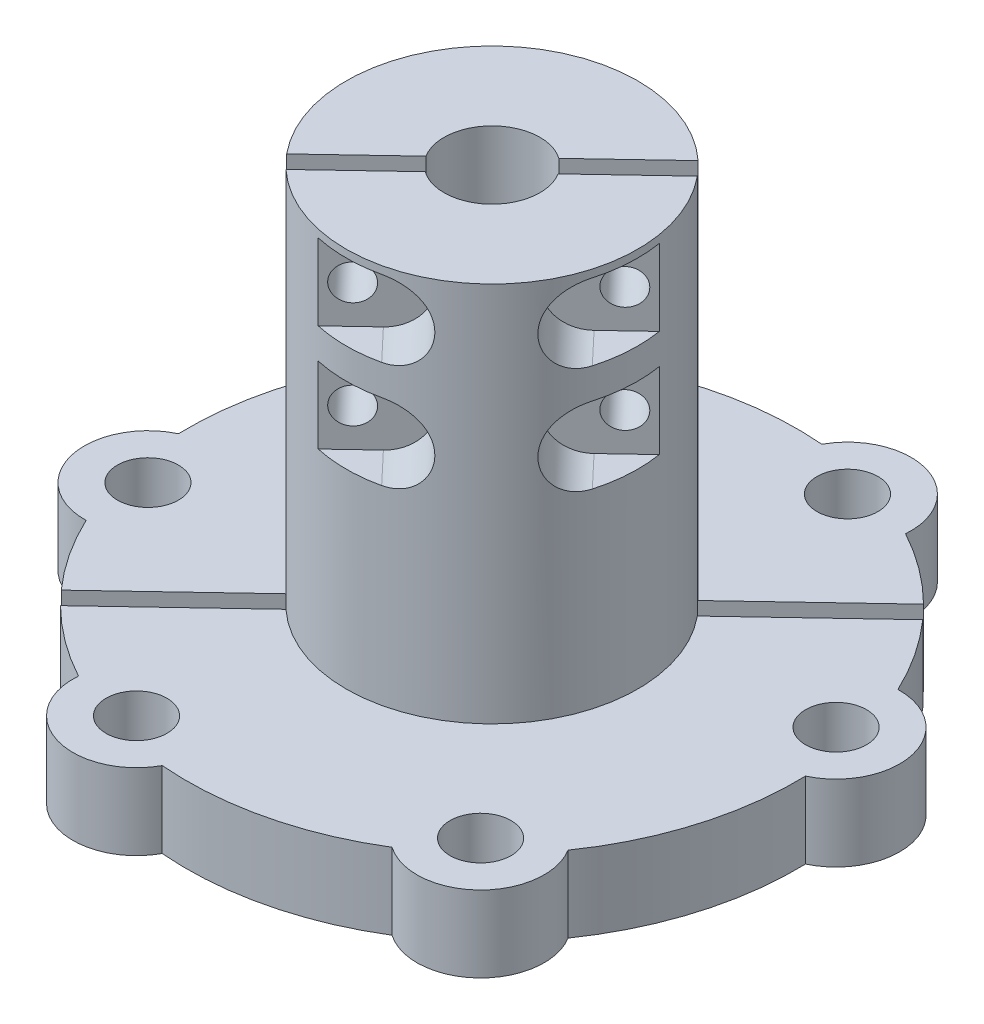
SolidWorks part; units mm, degrees
ref_plane "Front" through (0, 0, 0) normal (0, 0, 1) x (1, 0, 0)
ref_plane "Top" through (0, 0, 0) normal (0, 1, 0) x (1, 0, 0)
ref_plane "Right" through (0, 0, 0) normal (1, 0, 0) x (0, 0, -1)
sketch "Sketch1" plane through (0, 0, 0) normal (0, 1, 0) x (1, 0, 0)
  circle A0 centre (0, 0) radius 29.3688
  circle A1 centre (0, 0) radius 4
  dimension "D1" = 58.7375
  dimension "D2" = 8
extrude "Boss-Extrude1" add sketch "Sketch1" along normal blind 6.35
sketch "Sketch3" plane through (0, 6.35, 0) normal (0, 1, 0) x (1, 0, 0)
  circle A0 centre (0, 0) radius 4 construction
  circle A1 centre (0, 0) radius 4
  circle A2 centre (0, 0) radius 12.1539
  dimension "D1" = 24.3078
extrude "Boss-Extrude2" add sketch "Sketch3" along normal blind 31.75
sketch "Sketch4" plane through (0, 6.35, 0) normal (0, 1, 0) x (1, 0, 0)
  circle A0 centre (0, 0) radius 51.9218
  arc A1 (25.4208, 0.7099) -> (23.0191, 10.8093) centre (23.1665, 5.5091) ccw
  arc A2 (23.0191, 10.8093) -> (12.0949, 22.3703) centre (0, 0) ccw
  arc A3 (12.0949, 22.3703) -> (2.1481, 25.3398) centre (6.8115, 22.8166) ccw
  arc A4 (2.1481, 25.3398) -> (-13.3267, 21.6591) centre (0, 0) ccw
  arc A5 (-13.3267, 21.6591) -> (-20.8715, 14.5293) centre (-16.3548, 17.3065) ccw
  arc A6 (-20.8715, 14.5293) -> (-25.4207, -0.7121) centre (0, 0) ccw
  arc A7 (-25.4207, -0.7121) -> (-23.0182, -10.8112) centre (-23.166, -5.5111) ccw
  arc A8 (-23.0182, -10.8112) -> (-12.0943, -22.3707) centre (0, 0) ccw
  arc A9 (-12.0943, -22.3707) -> (-2.1466, -25.3399) centre (-6.811, -22.8186) ccw
  arc A10 (-2.1466, -25.3399) -> (13.3255, -21.6599) centre (0, 0) ccw
  arc A11 (13.3255, -21.6599) -> (20.8711, -14.5299) centre (16.3552, -17.3085) ccw
  arc A12 (25.6787, 0.5533) -> (23.1789, 11.0653) centre (23.1665, 5.5091) ccw
  arc A13 (21.1727, -14.5402) -> (25.6787, 0.5533) centre (0, 0) ccw
  arc A14 (13.3188, -21.9616) -> (21.1727, -14.5402) centre (16.3552, -17.3085) ccw
  arc A15 (-2.0047, -25.6063) -> (13.3188, -21.9616) centre (0, 0) ccw
  arc A16 (-12.359, -22.5157) -> (-2.0047, -25.6063) centre (-6.811, -22.8186) ccw
  arc A17 (-23.178, -11.0673) -> (-12.359, -22.5157) centre (0, 0) ccw
  arc A18 (-25.6787, -0.5554) -> (-23.178, -11.0673) centre (-23.166, -5.5111) ccw
  arc A19 (-21.1731, 14.5397) -> (-25.6787, -0.5554) centre (0, 0) ccw
  arc A20 (-13.3201, 21.9608) -> (-21.1731, 14.5397) centre (-16.3548, 17.3065) ccw
  arc A21 (2.0063, 25.6062) -> (-13.3201, 21.9608) centre (0, 0) ccw
  arc A22 (12.3596, 22.5154) -> (2.0063, 25.6062) centre (6.8115, 22.8166) ccw
  arc A23 (23.1789, 11.0653) -> (12.3596, 22.5154) centre (0, 0) ccw
  arc A24 (25.6787, 0.5533) -> (23.1789, 11.0653) centre (23.1665, 5.5091) ccw construction
  arc A25 (21.1727, -14.5402) -> (25.6787, 0.5533) centre (0, 0) ccw construction
  arc A26 (13.3188, -21.9616) -> (21.1727, -14.5402) centre (16.3552, -17.3085) ccw construction
  arc A27 (-2.0047, -25.6063) -> (13.3188, -21.9616) centre (0, 0) ccw construction
  arc A28 (-12.359, -22.5157) -> (-2.0047, -25.6063) centre (-6.811, -22.8186) ccw construction
  arc A29 (-23.178, -11.0673) -> (-12.359, -22.5157) centre (0, 0) ccw construction
  arc A30 (-25.6787, -0.5554) -> (-23.178, -11.0673) centre (-23.166, -5.5111) ccw construction
  arc A31 (-21.1731, 14.5397) -> (-25.6787, -0.5554) centre (0, 0) ccw construction
  arc A32 (-13.3201, 21.9608) -> (-21.1731, 14.5397) centre (-16.3548, 17.3065) ccw construction
  arc A33 (2.0063, 25.6062) -> (-13.3201, 21.9608) centre (0, 0) ccw construction
  arc A34 (12.3596, 22.5154) -> (2.0063, 25.6062) centre (6.8115, 22.8166) ccw construction
  arc A35 (23.1789, 11.0653) -> (12.3596, 22.5154) centre (0, 0) ccw construction
  arc A36 (20.8711, -14.5299) -> (25.4208, 0.7099) centre (0, 0) ccw
  dimension "D2" = 0.254
  dimension "D1" = 0
extrude "Cut-Extrude1" cut sketch "Sketch4" against normal through all
sketch "Sketch5" plane through (0, 6.35, 0) normal (0, 1, 0) x (1, 0, 0)
  circle A0 centre (-23.166, -5.5111) radius 2.54 construction
  circle A1 centre (-6.811, -22.8186) radius 2.54 construction
  circle A2 centre (16.3552, -17.3085) radius 2.54 construction
  circle A3 centre (23.1665, 5.5091) radius 2.54 construction
  circle A4 centre (6.8115, 22.8166) radius 2.54 construction
  circle A5 centre (-16.3548, 17.3065) radius 2.54 construction
  circle A6 centre (-23.166, -5.5111) radius 2.54
  circle A7 centre (-6.811, -22.8186) radius 2.54
  circle A8 centre (16.3552, -17.3085) radius 2.54
  circle A9 centre (23.1665, 5.5091) radius 2.54
  circle A10 centre (6.8115, 22.8166) radius 2.54
  circle A11 centre (-16.3548, 17.3065) radius 2.54
extrude "Cut-Extrude2" cut sketch "Sketch5" against normal through all
sketch "Sketch6" plane through (0, 0, 0) normal (0, -1, 0) x (1, 0, 0)
  circle A0 centre (0, 0) radius 11.1125
  dimension "D1" = 22.225
extrude "Cut-Extrude3" cut sketch "Sketch6" against normal blind 12.7
sketch "Outline" plane through (0, 0, 0) normal (0, -1, 0) x (1, 0, 0)
  circle A0 centre (0, 0) radius 11.1125 construction
  circle A1 centre (0, 0) radius 11.1125
  arc A12 (25.4208, -0.7099) -> (20.8711, 14.5299) centre (0, 0) ccw
  arc A13 (20.8711, 14.5299) -> (13.3255, 21.6599) centre (16.3552, 17.3085) ccw
  arc A14 (13.3255, 21.6599) -> (-2.1466, 25.3399) centre (0, 0) ccw
  arc A15 (-2.1466, 25.3399) -> (-12.0943, 22.3707) centre (-6.811, 22.8186) ccw
  arc A16 (-12.0943, 22.3707) -> (-23.0182, 10.8112) centre (0, 0) ccw
  arc A17 (-23.0182, 10.8112) -> (-25.4207, 0.7121) centre (-23.166, 5.5111) ccw
  arc A18 (-25.4207, 0.7121) -> (-20.8715, -14.5293) centre (0, 0) ccw
  arc A19 (-20.8715, -14.5293) -> (-13.3267, -21.6591) centre (-16.3548, -17.3065) ccw
  arc A20 (-13.3267, -21.6591) -> (2.1481, -25.3398) centre (0, 0) ccw
  arc A21 (2.1481, -25.3398) -> (12.0949, -22.3703) centre (6.8115, -22.8166) ccw
  arc A22 (12.0949, -22.3703) -> (23.0191, -10.8093) centre (0, 0) ccw
  arc A23 (23.0191, -10.8093) -> (25.4208, -0.7099) centre (23.1665, -5.5091) ccw
  arc A24 (25.4208, -0.7099) -> (20.8711, 14.5299) centre (0, 0) ccw
  arc A25 (20.8711, 14.5299) -> (13.3255, 21.6599) centre (16.3552, 17.3085) ccw
  arc A26 (13.3255, 21.6599) -> (-2.1466, 25.3399) centre (0, 0) ccw
  arc A27 (-2.1466, 25.3399) -> (-12.0943, 22.3707) centre (-6.811, 22.8186) ccw
  arc A28 (-12.0943, 22.3707) -> (-23.0182, 10.8112) centre (0, 0) ccw
  arc A29 (-23.0182, 10.8112) -> (-25.4207, 0.7121) centre (-23.166, 5.5111) ccw
  arc A30 (-25.4207, 0.7121) -> (-20.8715, -14.5293) centre (0, 0) ccw
  arc A31 (-20.8715, -14.5293) -> (-13.3267, -21.6591) centre (-16.3548, -17.3065) ccw
  arc A32 (-13.3267, -21.6591) -> (2.1481, -25.3398) centre (0, 0) ccw
  arc A33 (2.1481, -25.3398) -> (12.0949, -22.3703) centre (6.8115, -22.8166) ccw
  arc A34 (12.0949, -22.3703) -> (23.0191, -10.8093) centre (0, 0) ccw
  arc A35 (23.0191, -10.8093) -> (25.4208, -0.7099) centre (23.1665, -5.5091) ccw
  dimension "D1" = 0
sketch "Sketch7" plane through (0, 0, 0) normal (0, -1, 0) x (1, 0, 0)
  line L0 (-18.4831, 17.4669) -> (18.4841, -17.4659) construction
  line L1 (-23.8841, 21.4785) -> (22.7947, -22.6313)
  line L2 (-22.7937, 22.6323) -> (23.885, -21.4775)
  line L3 (-17.938, 18.0438) -> (19.0293, -16.889) construction
  line L4 (-19.0283, 16.89) -> (17.9389, -18.0428) construction
  arc A0 (-12.0943, 22.3707) -> (-23.0182, 10.8112) centre (0, 0) ccw construction
  arc A1 (12.0949, -22.3703) -> (23.0191, -10.8093) centre (0, 0) ccw construction
  arc A2 (-22.7937, 22.6323) -> (-23.8841, 21.4785) centre (0, 0) ccw
  arc A3 (22.7947, -22.6313) -> (23.885, -21.4775) centre (0, 0) ccw
  dimension "D1" = 0.7937
  dimension "D2" = 0.7937
extrude "Slot" cut sketch "Sketch7" against normal through all
ref_plane "Plane1" through (-25.6223, 0, -27.1146) normal (-0.6868, 0, -0.7268) x (-0.7268, 0, 0.6868)
sketch "Sketch8" plane through (-25.6223, 0, -27.1146) normal (-0.6868, 0, -0.7268) x (-0.7268, 0, 0.6868)
  line L0 (8.0241, 38.1) -> (8.0241, 34.29) construction
  line L1 (8.0241, 34.29) -> (8.0241, 25.4) construction
  line L2 (3.9203, 12.7) -> (-3.9203, 12.7) construction
  line L3 (0, 12.7) -> (0, 58.6753) construction
  line L8 (12.1279, 38.1) -> (3.9203, 38.1)
  line L9 (3.9203, 38.1) -> (3.9203, 12.7)
  line L10 (3.9203, 12.7) -> (11.0841, 12.7)
  line L11 (11.0841, 12.7) -> (11.0841, 0)
  line L12 (11.0841, 0) -> (25.4183, 0)
  line L13 (25.4183, 0) -> (25.4183, 6.35)
  line L14 (25.4183, 6.35) -> (12.1279, 6.35)
  line L15 (12.1279, 6.35) -> (12.1279, 38.1)
  line L16 (12.1279, 38.1) -> (3.9203, 38.1) construction
  line L17 (3.9203, 38.1) -> (3.9203, 12.7) construction
  line L18 (3.9203, 12.7) -> (11.0841, 12.7) construction
  line L19 (11.0841, 12.7) -> (11.0841, 0) construction
  line L20 (11.0841, 0) -> (25.4183, 0) construction
  line L21 (25.4183, 0) -> (25.4183, 6.35) construction
  line L22 (25.4183, 6.35) -> (12.1279, 6.35) construction
  line L23 (12.1279, 6.35) -> (12.1279, 38.1) construction
  line L24 (-12.1279, 6.35) -> (-25.4183, 6.35)
  line L25 (-25.4183, 6.35) -> (-25.4183, 0)
  line L26 (-25.4183, 0) -> (-11.0841, 0)
  line L27 (-11.0841, 0) -> (-11.0841, 12.7)
  line L28 (-11.0841, 12.7) -> (-3.9203, 12.7)
  line L29 (-3.9203, 12.7) -> (-3.9203, 38.1)
  line L30 (-3.9203, 38.1) -> (-12.1279, 38.1)
  line L31 (-12.1279, 38.1) -> (-12.1279, 6.35)
  line L32 (-12.1279, 6.35) -> (-25.4183, 6.35) construction
  line L33 (-25.4183, 6.35) -> (-25.4183, 0) construction
  line L34 (-25.4183, 0) -> (-11.0841, 0) construction
  line L35 (-11.0841, 0) -> (-11.0841, 12.7) construction
  line L36 (-11.0841, 12.7) -> (-3.9203, 12.7) construction
  line L37 (-3.9203, 12.7) -> (-3.9203, 38.1) construction
  line L38 (-3.9203, 38.1) -> (-12.1279, 38.1) construction
  line L39 (-12.1279, 38.1) -> (-12.1279, 6.35) construction
  circle A0 centre (8.0241, 34.29) radius 1.4732
  circle A1 centre (8.0241, 25.4) radius 1.4732
  circle A2 centre (-8.0241, 34.29) radius 1.4732
  circle A3 centre (-8.0241, 25.4) radius 1.4732
  dimension "D4" = 2.9464
  dimension "D3" = 3.81
  dimension "D5" = 8.89
  dimension "D1" = 0
  dimension "D2" = 0
extrude "No4-40 Holes" cut sketch "Sketch8" against normal through all
sketch "Sketch9" plane through (-25.6223, 0, -27.1146) normal (-0.6868, 0, -0.7268) x (-0.7268, 0, 0.6868)
  circle A0 centre (-8.0241, 25.4) radius 1.4732 construction
  circle A1 centre (8.0241, 34.29) radius 1.4732 construction
  circle A2 centre (8.0241, 25.4) radius 1.4732 construction
  circle A3 centre (-8.0241, 25.4) radius 1.4732 construction
  circle A4 centre (8.0241, 34.29) radius 1.4732 construction
  circle A5 centre (8.0241, 25.4) radius 1.4732 construction
  circle A6 centre (-8.0241, 34.29) radius 1.4732 construction
  circle A7 centre (-8.0241, 34.29) radius 1.4732 construction
  circle A8 centre (8.0241, 25.4) radius 2.413
  circle A9 centre (8.0241, 34.29) radius 2.413
  circle A10 centre (-8.0241, 25.4) radius 2.413
  circle A11 centre (-8.0241, 34.29) radius 2.413
  dimension "D1" = 4.826
extrude "No4-40 Counterbore" cut sketch "Sketch9" against normal blind 30.48
ref_plane "Plane2" through (25.6233, 0, 27.1156) normal (0.6868, 0, 0.7268) x (0.7268, 0, -0.6868)
sketch "Sketch10" plane through (25.6233, 0, 27.1156) normal (0.6868, 0, 0.7268) x (0.7268, 0, -0.6868)
  line L0 (6.2101, 37.465) -> (22.6115, 37.465)
  line L13 (6.2101, 31.115) -> (22.6115, 31.115)
  line L14 (22.6115, 31.115) -> (22.6115, 37.465)
  line L15 (6.2101, 28.575) -> (22.6115, 28.575)
  line L16 (22.6115, 28.575) -> (22.6115, 22.225)
  line L17 (22.6115, 22.225) -> (6.2101, 22.225)
  line L18 (-8.0241, 34.29) -> (8.0432, 34.29) construction
  line L19 (0, 31.115) -> (0, 14.3016) construction
  line L20 (-22.6115, 22.225) -> (-6.2101, 22.225)
  line L21 (-22.6115, 28.575) -> (-22.6115, 22.225)
  line L22 (-6.2101, 28.575) -> (-22.6115, 28.575)
  line L23 (-22.6115, 31.115) -> (-22.6115, 37.465)
  line L24 (-6.2101, 31.115) -> (-22.6115, 31.115)
  line L25 (-6.2101, 37.465) -> (-22.6115, 37.465)
  line L26 (3.0351, 25.4) -> (22.6115, 25.4) construction
  arc A6 (6.2101, 37.465) -> (6.2101, 31.115) centre (6.2101, 34.29) ccw
  arc A7 (6.2101, 28.575) -> (6.2101, 22.225) centre (6.2101, 25.4) ccw
  circle A8 centre (-8.0241, 34.29) radius 1.4732 construction
  circle A9 centre (-8.0241, 34.29) radius 1.4732 construction
  arc A10 (-6.2101, 28.575) -> (-6.2101, 22.225) centre (-6.2101, 25.4) cw
  arc A11 (-6.2101, 37.465) -> (-6.2101, 31.115) centre (-6.2101, 34.29) cw
  circle A12 centre (8.0241, 25.4) radius 1.4732 construction
  circle A13 centre (8.0241, 25.4) radius 1.4732 construction
  point P15 (0, 0)
  dimension "D1" = 6.35
extrude "No4-40 Nut Slots" cut sketch "Sketch10" against normal blind 30.48
sketch "Sketch12" plane through (0, 38.1, 0) normal (0, 1, 0) x (1, 0, 0)
  line L0 (-2.7473, 2.9073) -> (2.7473, -2.9073) construction
  line L1 (0, 0) -> (-2.0299, -1.9182) construction
  line L2 (-19.9965, 21.1603) -> (-26.1686, 27.6915) construction
  line L3 (-19.9965, 21.1603) -> (-8.3478, 8.8336) construction
  arc A0 (2.3049, 3.2692) -> (-3.3943, -2.1164) centre (0, 0) ccw construction
  arc A1 (-2.3037, -3.27) -> (3.395, 2.1151) centre (0, 0) ccw construction
  circle A2 centre (0, 0) radius 38.1
  arc A3 (-13.3267, 21.6591) -> (-20.8715, 14.5293) centre (-16.3548, 17.3065) ccw construction
  arc A4 (-13.3267, 21.6591) -> (-20.8715, 14.5293) centre (-16.3548, 17.3065) ccw
  circle A5 centre (0, 0) radius 12.1539 construction
  arc A7 (8.2702, 8.9062) -> (-9.3596, -7.7534) centre (0, 0) ccw construction
  dimension "D1" = 76.2
sketch "Sketch13" plane through (4.6889, 0, 4.962) normal (0.6868, 0, 0.7268) x (0.7268, 0, -0.6868)
  line L0 (-8.0241, 34.29) -> (0, 34.29) construction
  line L1 (0, 38.1) -> (0, 25.4) construction
  line L2 (12.1279, 38.1) -> (-12.1279, 38.1) construction
  line L3 (12.1279, 38.1) -> (-12.1279, 38.1)
  line L4 (-8.0241, 25.4) -> (0, 25.4) construction
  arc A2 (-10.0563, 24.0989) -> (-10.0563, 26.7011) centre (-8.0241, 25.4) ccw construction
  arc A3 (-10.0563, 24.0989) -> (-10.0563, 26.7011) centre (-8.0241, 25.4) ccw
  arc A4 (-10.0563, 32.9889) -> (-10.0563, 35.5911) centre (-8.0241, 34.29) ccw construction
  arc A5 (-10.0563, 32.9889) -> (-10.0563, 35.5911) centre (-8.0241, 34.29) ccw
  dimension "D1" = 3.81
  dimension "D2" = 12.7
  dimension "D3" = 8.0241
sketch "Sketch14" plane through (0, 38.1, 0) normal (0, 1, 0) x (1, 0, 0)
  line L0 (4.6889, -4.962) -> (8.3476, -8.8337) construction
  line L4 (9.2026, -0.6967) -> (11.6893, -3.3283) construction
  line L5 (9.2026, -0.6967) -> (11.6893, -3.3283)
  line L6 (13.5038, 3.3677) -> (-4.1259, -13.2917) construction
  line L7 (13.5038, 3.3677) -> (-4.1259, -13.2917)
  arc A1 (-8.2692, -8.9072) -> (9.3605, 7.7523) centre (0, 0) ccw construction
  dimension "D1" = 5.3269
